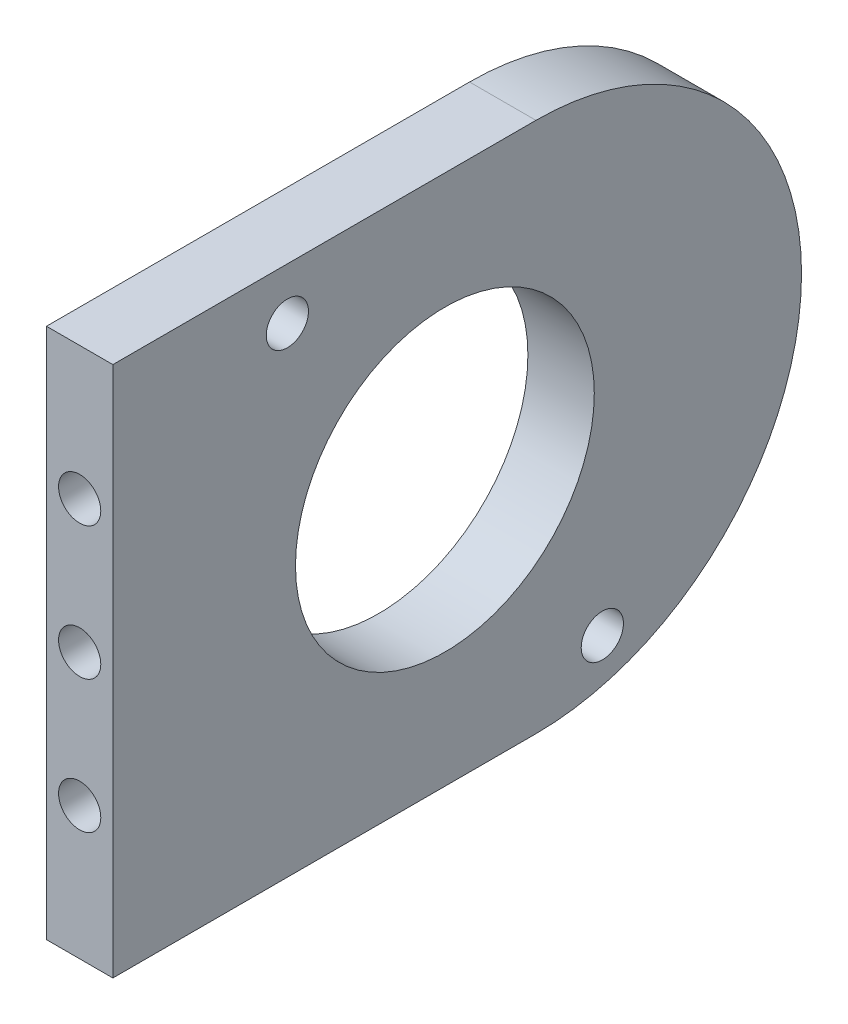
SolidWorks part; units mm, degrees
material "6061-T6 (SS)"
ref_plane "Front" through (0, 0, 0) normal (0, 0, 1) x (1, 0, 0)
ref_plane "Top" through (0, 0, 0) normal (0, 1, 0) x (1, 0, 0)
ref_plane "Right" through (0, 0, 0) normal (1, 0, 0) x (0, 0, -1)
sketch "Sketch2" plane through (0, 0, 0) normal (1, 0, 0) x (0, 0, -1)
  line L1 (-38.1, -25.4) -> (38.1, -25.4)
  line L2 (-38.1, -25.4) -> (-38.1, 25.4)
  line L3 (-38.1, 25.4) -> (38.1, 25.4)
  line L4 (38.1, -25.4) -> (38.1, 25.4)
  line L5 (-38.1, -25.4) -> (38.1, 25.4) construction
  line L6 (-38.1, 25.4) -> (38.1, -25.4) construction
  point P0 (0, 0)
  dimension "D1" = 76.2
  dimension "D2" = 50.8
extrude "Boss-Extrude2" add sketch "Sketch2" along normal blind 6.35
hole_wizard "#10-32 Tapped Hole1" positions "Sketch3" profile "Sketch5" tap size "#10-32" standard "ANSI Inch"
sketch "Sketch3" plane through (0, 0, 38.1) normal (0, 0, 1) x (1, 0, 0)
  line L0 (3.175, 25.4) -> (3.175, 12.7) construction
  line L1 (6.35, 25.4) -> (0, 25.4) construction
  line L3 (3.175, 12.7) -> (3.175, 0) construction
  line L4 (3.175, 0) -> (3.175, -12.7) construction
  line L5 (3.175, -12.7) -> (3.175, -25.4) construction
  line L6 (6.35, -25.4) -> (0, -25.4) construction
  point P0 (3.175, -12.7)
  point P2 (3.175, 0)
  point P6 (3.175, 12.7)
sketch "Sketch5" plane through (3.175, -12.7, 38.1) normal (1, 0, 0) x (0, -1, 0)
  line L0 (0, 0) -> (0, 13.2428)
  line L1 (0, 13.2428) -> (2.0193, 12.0294)
  line L2 (2.0193, 12.0294) -> (2.0193, 0)
  line L5 (2.0193, 0) -> (0, 0)
  line L10 (0, 13.2428) -> (-2.0193, 12.0294) construction
  line L11 (0, -6.35) -> (0, 107.95) construction
  dimension "Tap Drill Dia." = 4.0386
  dimension "Tap Drill Depth" = 12.0294
  dimension "Drill Angle" = 118
cosmetic thread "Hole Thread1" parameters "D1"=9.652, "D2"=4.826
cosmetic thread "Hole Thread3" parameters "D1"=9.652, "D2"=4.826
cosmetic thread "Hole Thread4" parameters "D1"=9.652, "D2"=4.826
sketch "Sketch6" plane through (6.35, 0, 0) normal (1, 0, 0) x (0, 0, -1)
  line L0 (-38.1, 25.4) -> (-38.1, -25.4) construction
  line L1 (-38.1, -25.4) -> (38.1, -25.4) construction
  circle A0 centre (-6.35, 0) radius 14.2875
  dimension "D1" = 31.75
  dimension "D3" = 28.575
  dimension "D2" = 25.4
extrude "Cut-Extrude1" cut sketch "Sketch6" against normal through all
sketch "Sketch10" plane through (0, 0, 0) normal (-1, 0, 0) x (0, 0, 1)
  point P3 (-8.7041, -20.4408)
  point P8 (21.4132, 20.4687)
hole_wizard "#10-32 Tapped Hole2" positions "Sketch10" profile "Sketch9" tap size "#10-32" standard "ANSI Inch"
sketch "Sketch9" plane through (0, -20.4408, -8.7041) normal (0, 1, 0) x (0, 0, 1)
  line L0 (0, 0) -> (0, 13.2428)
  line L1 (0, 13.2428) -> (2.0193, 12.0294)
  line L2 (2.0193, 12.0294) -> (2.0193, 0)
  line L5 (2.0193, 0) -> (0, 0)
  line L10 (0, 13.2428) -> (-2.0193, 12.0294) construction
  line L11 (0, -6.35) -> (0, 107.95) construction
  dimension "Tap Drill Dia." = 4.0386
  dimension "Tap Drill Depth" = 12.0294
  dimension "Drill Angle" = 118
cosmetic thread "Hole Thread5" parameters "D1"=9.652, "D2"=4.826
cosmetic thread "Hole Thread6" parameters "D1"=9.652, "D2"=4.826
sketch "Sketch13" plane through (6.35, 0, 0) normal (1, 0, 0) x (0, 0, -1)
  line L0 (27.7541, -25.4) -> (27.7541, 25.4)
  line L1 (-38.1, -25.4) -> (38.1, -25.4) construction
  line L2 (38.1, 25.4) -> (-38.1, 25.4) construction
  line L3 (27.7541, 25.4) -> (38.1, 25.4)
  line L4 (38.1, 25.4) -> (38.1, -25.4)
  line L5 (38.1, -25.4) -> (27.7541, -25.4)
  circle A0 centre (8.7041, -20.4408) radius 2.0193 construction
  dimension "D1" = 19.05
extrude "Cut-Extrude2" cut sketch "Sketch13" against normal through all
fillet "Fillet3" radius 25.4 2 edges at (3.175, 25.4, -27.7541) (3.175, -25.4, -27.7541)
